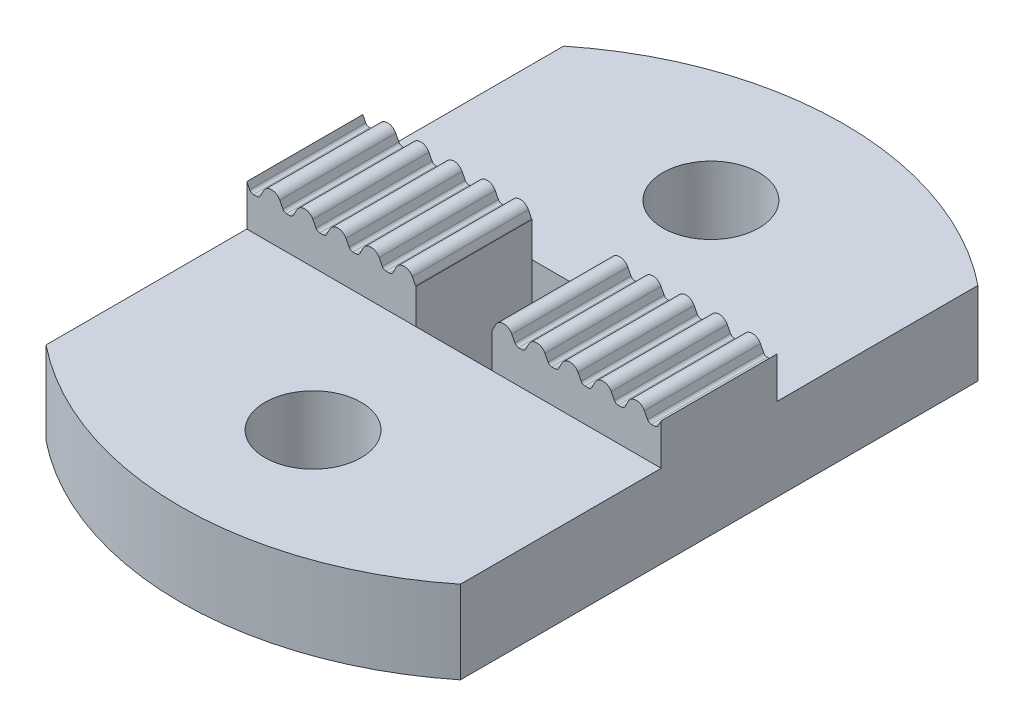
SolidWorks part; units mm, degrees
ref_plane "Front Plane" through (0, 0, 0) normal (0, 0, 1) x (1, 0, 0)
ref_plane "Top Plane" through (0, 0, 0) normal (0, 1, 0) x (1, 0, 0)
ref_plane "Right Plane" through (0, 0, 0) normal (1, 0, 0) x (0, 0, -1)
sketch "Sketch1" plane through (0, 0, 0) normal (0, 0, 1) x (1, 0, 0)
  line L0 (1.09, 0.25) -> (1.99, 0.25) construction
  line L1 (3.5789, 0.502) -> (3.7678, 0.1355)
  line L2 (3.99, 0) -> (4.18, 0)
  line L3 (1.5789, 0.502) -> (1.7678, 0.1355)
  line L4 (1.99, 0) -> (2.18, 0)
  line L5 (0.4122, 0.1355) -> (0.6011, 0.502)
  line L6 (1.09, 0.25) -> (0.19, 0.25) construction
  line L7 (0.19, 0) -> (0, 0)
  line L8 (2.4122, 0.1355) -> (2.6011, 0.502)
  line L9 (2.19, 0) -> (2, 0)
  line L10 (5.5789, 0.502) -> (5.7678, 0.1355)
  line L11 (5.99, 0) -> (6.18, 0)
  line L12 (4.4122, 0.1355) -> (4.6011, 0.502)
  line L13 (4.19, 0) -> (4, 0)
  line L14 (7.5789, 0.502) -> (7.7678, 0.1355)
  line L15 (7.99, 0) -> (8.18, 0)
  line L16 (6.4122, 0.1355) -> (6.6011, 0.502)
  line L17 (6.19, 0) -> (6, 0)
  line L18 (9.5789, 0.502) -> (9.7678, 0.1355)
  line L19 (9.99, 0) -> (10.18, 0)
  line L20 (8.4122, 0.1355) -> (8.6011, 0.502)
  line L21 (8.19, 0) -> (8, 0)
  line L22 (11.5789, 0.502) -> (11.7678, 0.1355)
  line L23 (11.99, 0) -> (12.18, 0)
  line L24 (10.4122, 0.1355) -> (10.6011, 0.502)
  line L25 (10.19, 0) -> (10, 0)
  line L26 (13.5789, 0.502) -> (13.7678, 0.1355)
  line L27 (13.99, 0) -> (14.18, 0)
  line L28 (12.4122, 0.1355) -> (12.6011, 0.502)
  line L29 (12.19, 0) -> (12, 0)
  line L30 (1.5789, 0.502) -> (3.5789, 0.502) construction
  line L31 (0, 0) -> (0, -5)
  line L32 (0, -5) -> (36.18, -5)
  line L33 (36.18, -5) -> (36.18, 0)
  line L34 (14.18, 0) -> (0, 0) construction
  line L35 (15.5789, 0.502) -> (15.7678, 0.1355)
  line L36 (15.99, 0) -> (16.18, 0)
  line L37 (14.4122, 0.1355) -> (14.6011, 0.502)
  line L38 (14.19, 0) -> (14, 0)
  line L39 (17.5789, 0.502) -> (17.7678, 0.1355)
  line L40 (17.99, 0) -> (18.18, 0)
  line L41 (16.4122, 0.1355) -> (16.6011, 0.502)
  line L42 (16.19, 0) -> (16, 0)
  line L43 (19.5789, 0.502) -> (19.7678, 0.1355)
  line L44 (19.99, 0) -> (20.18, 0)
  line L45 (18.4122, 0.1355) -> (18.6011, 0.502)
  line L46 (18.19, 0) -> (18, 0)
  line L47 (21.5789, 0.502) -> (21.7678, 0.1355)
  line L48 (21.99, 0) -> (22.18, 0)
  line L49 (20.4122, 0.1355) -> (20.6011, 0.502)
  line L50 (20.19, 0) -> (20, 0)
  line L51 (23.5789, 0.502) -> (23.7678, 0.1355)
  line L52 (23.99, 0) -> (24.18, 0)
  line L53 (22.4122, 0.1355) -> (22.6011, 0.502)
  line L54 (22.19, 0) -> (22, 0)
  line L55 (25.5789, 0.502) -> (25.7678, 0.1355)
  line L56 (25.99, 0) -> (26.18, 0)
  line L57 (24.4122, 0.1355) -> (24.6011, 0.502)
  line L58 (24.19, 0) -> (24, 0)
  line L59 (27.5789, 0.502) -> (27.7678, 0.1355)
  line L60 (27.99, 0) -> (28.18, 0)
  line L61 (26.4122, 0.1355) -> (26.6011, 0.502)
  line L62 (26.19, 0) -> (26, 0)
  line L63 (29.5789, 0.502) -> (29.7678, 0.1355)
  line L64 (29.99, 0) -> (30.18, 0)
  line L65 (28.4122, 0.1355) -> (28.6011, 0.502)
  line L66 (28.19, 0) -> (28, 0)
  line L67 (31.5789, 0.502) -> (31.7678, 0.1355)
  line L68 (31.99, 0) -> (32.18, 0)
  line L69 (30.4122, 0.1355) -> (30.6011, 0.502)
  line L70 (30.19, 0) -> (30, 0)
  line L71 (33.5789, 0.502) -> (33.7678, 0.1355)
  line L72 (33.99, 0) -> (34.18, 0)
  line L73 (32.4122, 0.1355) -> (32.6011, 0.502)
  line L74 (32.19, 0) -> (32, 0)
  line L75 (35.5789, 0.502) -> (35.7678, 0.1355)
  line L76 (35.99, 0) -> (36.18, 0)
  line L77 (34.4122, 0.1355) -> (34.6011, 0.502)
  line L78 (34.19, 0) -> (34, 0)
  arc A0 (1.5789, 0.502) -> (0.6011, 0.502) centre (1.09, 0.25) ccw
  arc A1 (1.7678, 0.1355) -> (1.99, 0) centre (1.99, 0.25) ccw
  arc A2 (0.19, 0) -> (0.4122, 0.1355) centre (0.19, 0.25) ccw
  arc A3 (3.5789, 0.502) -> (2.6011, 0.502) centre (3.09, 0.25) ccw
  arc A4 (3.7678, 0.1355) -> (3.99, 0) centre (3.99, 0.25) ccw
  arc A5 (2.19, 0) -> (2.4122, 0.1355) centre (2.19, 0.25) ccw
  arc A6 (5.5789, 0.502) -> (4.6011, 0.502) centre (5.09, 0.25) ccw
  arc A7 (5.7678, 0.1355) -> (5.99, 0) centre (5.99, 0.25) ccw
  arc A8 (4.19, 0) -> (4.4122, 0.1355) centre (4.19, 0.25) ccw
  arc A9 (7.5789, 0.502) -> (6.6011, 0.502) centre (7.09, 0.25) ccw
  arc A10 (7.7678, 0.1355) -> (7.99, 0) centre (7.99, 0.25) ccw
  arc A11 (6.19, 0) -> (6.4122, 0.1355) centre (6.19, 0.25) ccw
  arc A12 (9.5789, 0.502) -> (8.6011, 0.502) centre (9.09, 0.25) ccw
  arc A13 (9.7678, 0.1355) -> (9.99, 0) centre (9.99, 0.25) ccw
  arc A14 (8.19, 0) -> (8.4122, 0.1355) centre (8.19, 0.25) ccw
  arc A15 (11.5789, 0.502) -> (10.6011, 0.502) centre (11.09, 0.25) ccw
  arc A16 (11.7678, 0.1355) -> (11.99, 0) centre (11.99, 0.25) ccw
  arc A17 (10.19, 0) -> (10.4122, 0.1355) centre (10.19, 0.25) ccw
  arc A18 (13.5789, 0.502) -> (12.6011, 0.502) centre (13.09, 0.25) ccw
  arc A19 (13.7678, 0.1355) -> (13.99, 0) centre (13.99, 0.25) ccw
  arc A20 (12.19, 0) -> (12.4122, 0.1355) centre (12.19, 0.25) ccw
  arc A21 (15.5789, 0.502) -> (14.6011, 0.502) centre (15.09, 0.25) ccw
  arc A22 (15.7678, 0.1355) -> (15.99, 0) centre (15.99, 0.25) ccw
  arc A23 (14.19, 0) -> (14.4122, 0.1355) centre (14.19, 0.25) ccw
  arc A24 (17.5789, 0.502) -> (16.6011, 0.502) centre (17.09, 0.25) ccw
  arc A25 (17.7678, 0.1355) -> (17.99, 0) centre (17.99, 0.25) ccw
  arc A26 (16.19, 0) -> (16.4122, 0.1355) centre (16.19, 0.25) ccw
  arc A27 (19.5789, 0.502) -> (18.6011, 0.502) centre (19.09, 0.25) ccw
  arc A28 (19.7678, 0.1355) -> (19.99, 0) centre (19.99, 0.25) ccw
  arc A29 (18.19, 0) -> (18.4122, 0.1355) centre (18.19, 0.25) ccw
  arc A30 (21.5789, 0.502) -> (20.6011, 0.502) centre (21.09, 0.25) ccw
  arc A31 (21.7678, 0.1355) -> (21.99, 0) centre (21.99, 0.25) ccw
  arc A32 (20.19, 0) -> (20.4122, 0.1355) centre (20.19, 0.25) ccw
  arc A33 (23.5789, 0.502) -> (22.6011, 0.502) centre (23.09, 0.25) ccw
  arc A34 (23.7678, 0.1355) -> (23.99, 0) centre (23.99, 0.25) ccw
  arc A35 (22.19, 0) -> (22.4122, 0.1355) centre (22.19, 0.25) ccw
  arc A36 (25.5789, 0.502) -> (24.6011, 0.502) centre (25.09, 0.25) ccw
  arc A37 (25.7678, 0.1355) -> (25.99, 0) centre (25.99, 0.25) ccw
  arc A38 (24.19, 0) -> (24.4122, 0.1355) centre (24.19, 0.25) ccw
  arc A39 (27.5789, 0.502) -> (26.6011, 0.502) centre (27.09, 0.25) ccw
  arc A40 (27.7678, 0.1355) -> (27.99, 0) centre (27.99, 0.25) ccw
  arc A41 (26.19, 0) -> (26.4122, 0.1355) centre (26.19, 0.25) ccw
  arc A42 (29.5789, 0.502) -> (28.6011, 0.502) centre (29.09, 0.25) ccw
  arc A43 (29.7678, 0.1355) -> (29.99, 0) centre (29.99, 0.25) ccw
  arc A44 (28.19, 0) -> (28.4122, 0.1355) centre (28.19, 0.25) ccw
  arc A45 (31.5789, 0.502) -> (30.6011, 0.502) centre (31.09, 0.25) ccw
  arc A46 (31.7678, 0.1355) -> (31.99, 0) centre (31.99, 0.25) ccw
  arc A47 (30.19, 0) -> (30.4122, 0.1355) centre (30.19, 0.25) ccw
  arc A48 (33.5789, 0.502) -> (32.6011, 0.502) centre (33.09, 0.25) ccw
  arc A49 (33.7678, 0.1355) -> (33.99, 0) centre (33.99, 0.25) ccw
  arc A50 (32.19, 0) -> (32.4122, 0.1355) centre (32.19, 0.25) ccw
  arc A51 (35.5789, 0.502) -> (34.6011, 0.502) centre (35.09, 0.25) ccw
  arc A52 (35.7678, 0.1355) -> (35.99, 0) centre (35.99, 0.25) ccw
  arc A53 (34.19, 0) -> (34.4122, 0.1355) centre (34.19, 0.25) ccw
  dimension "D1" = 1.1
  dimension "D2" = 0.5
  dimension "D3" = 0.9
  dimension "D4" = 0.19
  dimension "D5" = 0.19
  dimension "D7" = 2
  dimension "D8" = 5
  dimension "D9" = 36.18
  dimension "D6" = 18
extrude "Boss-Extrude1" add sketch "Sketch1" along normal blind 7 contours A20 L29 L23 A16 L22 A15 L24 A17 L25 L19 A13 L18 A12 L20 A14 L21 L15 A10 L14 A9 L16 A11 L17 L11 A7 L10 A6 L12 A8 L13 L2 A4 L1 A3 L8 A5 L9 L4 A1 L3 A0 L5 A2 L7 L31 region at (18.09, -2.2826, 0)
sketch "Sketch2" plane through (0, 0, 0) normal (0, 1, 0) x (1, 0, 0)
  line L0 (0, -7) -> (36.18, 0) construction
  circle A0 centre (18.09, -3.5) radius 20
  dimension "D1" = 40
extrude "Boss-Extrude2" add sketch "Sketch2" against normal blind 5 from offset 2 offset against normal yes
sketch "Sketch4" plane through (0, -2, 0) normal (0, 1, 0) x (1, 0, 0)
  line L0 (0, 0) -> (36.18, 0)
  line L3 (15.79, 0) -> (20.39, 0)
  line L4 (15.79, 0) -> (15.79, -7)
  line L5 (15.79, -7) -> (20.39, -7)
  line L6 (20.39, 0) -> (20.39, -7)
  point P4 (18.09, 0)
  line M6 (36.18, -7) -> (0, -7)
  dimension "D1" = 7
  dimension "D2" = 4.6
extrude "Cut-Extrude2" cut sketch "Sketch4" against normal through all both and the other way through all contours L6 L0 L4 M6 region at (18.09, -2, 3.5)
sketch "Sketch5" plane through (0, -7, 0) normal (0, -1, 0) x (1, 0, 0)
  line L0 (18.09, 3.5) -> (18.09, 15.5) construction
  line L3 (18.09, 3.5) -> (18.09, -8.5) construction
  dimension "D1" = 12
hole_wizard "M5 Clearance Hole1" positions "3DSketch1" profile "Sketch6" hole size "M5" standard "ANSI Metric" end condition through all
sketch3d "3DSketch1"
  point P0 (18.09, -7, 15.5)
  point P3 (18.09, -7, -8.5)
sketch "Sketch6" plane through (18.09, -7, 15.5) normal (1, 0, 0) x (0, 0, -1)
  line L0 (0, 0) -> (0, 7.8)
  line L1 (0, 7.8) -> (2.9, 7.8)
  line L2 (2.9, 7.8) -> (2.9, 0)
  line L5 (2.9, 0) -> (0, 0)
  line L11 (0, -6.35) -> (0, 107.95) construction
  dimension "Thru Hole Dia." = 5.8
  dimension "Thru Hole Depth" = 7.8
sketch "Sketch7" plane through (0, -7, 0) normal (0, -1, 0) x (1, 0, 0)
  line L0 (18.09, 7) -> (18.09, 23.5) construction
  line L1 (5.59, 23.5) -> (30.59, 23.5)
  line L2 (5.59, 23.5) -> (5.59, -16.5)
  line L3 (5.59, -16.5) -> (30.59, -16.5)
  line L4 (30.59, 23.5) -> (30.59, -16.5)
  line L5 (20.39, 7) -> (15.79, 7) construction
  circle A0 centre (18.09, 3.5) radius 20 construction
  dimension "D1" = 25
extrude "Cut-Extrude3" cut sketch "Sketch7" against normal through all flip side to cut
